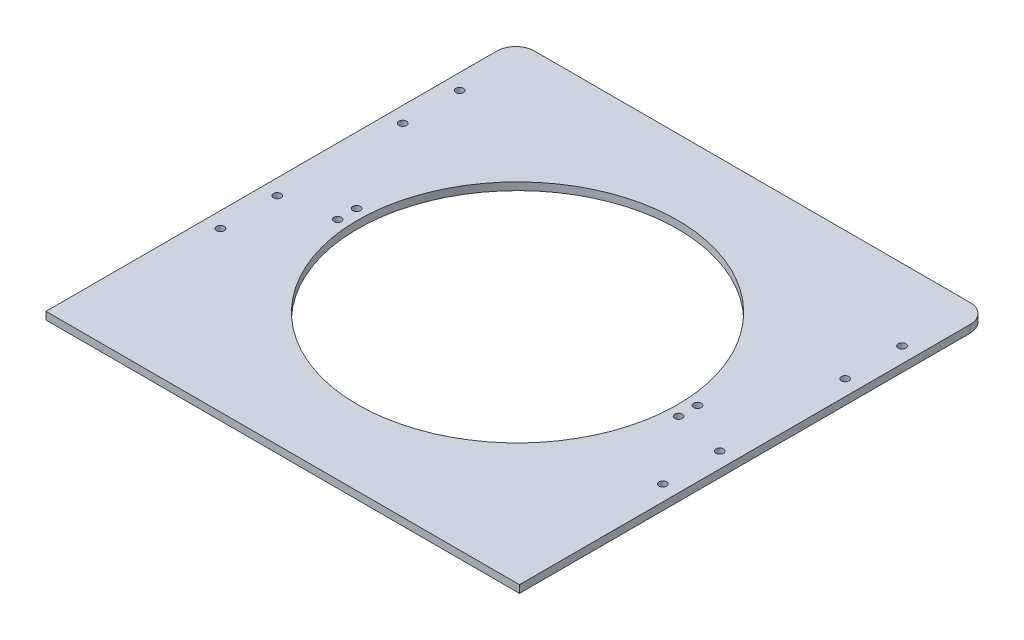
SolidWorks part; units mm, degrees
material "Medium density fiberboard, parallel to board"
ref_plane "Alzado" through (0, 0, 0) normal (0, 0, 1) x (1, 0, 0)
ref_plane "Planta" through (0, 0, 0) normal (0, 1, 0) x (1, 0, 0)
ref_plane "Vista lateral" through (0, 0, 0) normal (1, 0, 0) x (0, 0, -1)
sketch "Croquis1" plane through (0, 0, 0) normal (0, 1, 0) x (1, 0, 0)
  line L1 (-125, -124) -> (125, -124)
  line L2 (-125, -124) -> (-125, 114)
  line L3 (-115, 124) -> (115, 124)
  line L4 (125, -124) -> (125, 114)
  line L5 (-125, -124) -> (125, 124) construction
  line L6 (-125, 124) -> (125, -124) construction
  arc A0 (115, 124) -> (125, 114) centre (115, 114) cw
  arc A1 (-125, 114) -> (-115, 124) centre (-115, 114) cw
  point P0 (0, 0)
  dimension "D3" = 10
  dimension "D1" = 250
  dimension "D2" = 248
extrude "Saliente-Extruir1" add sketch "Croquis1" along normal blind 4
sketch "Croquis2" plane through (0, 4, 0) normal (0, 1, 0) x (1, 0, 0)
  line L0 (-125, 0) -> (125, 0) construction
  line L1 (-125, 114) -> (-125, -124) construction
  line L2 (125, -124) -> (125, 114) construction
  line L3 (0, 84.42) -> (0, -84.42) construction
  circle A0 centre (0, 0) radius 84.42
  circle A1 centre (-90, 5) radius 2
  circle A2 centre (-90, -5) radius 2
  circle A3 centre (90, -5) radius 2
  circle A4 centre (90, 5) radius 2
  dimension "D1" = 168.84
  dimension "D2" = 4
  dimension "D3" = 4
  dimension "D4" = 10
  dimension "D5" = 5
  dimension "D6" = 90
  dimension "D7" = 90
extrude "Cortar-Extruir1" cut sketch "Croquis2" against normal blind 4
sketch "Croquis3" plane through (0, 4, 0) normal (0, 1, 0) x (1, 0, 0)
  line L0 (115, 124) -> (-115, 124) construction
  line L1 (-125, 114) -> (-125, -124) construction
  line L2 (0, 33.527) -> (0, -33.527) construction
  circle A0 centre (-116.8, 86.2) radius 2
  circle A1 centre (-116.8, 56.15) radius 2
  circle A2 centre (-116.8, -10.05) radius 2
  circle A3 centre (-116.8, -40.1) radius 2
  circle A4 centre (116.8, -40.1) radius 2
  circle A5 centre (116.8, -10.05) radius 2
  circle A6 centre (116.8, 56.15) radius 2
  circle A7 centre (116.8, 86.2) radius 2
  point P15 (0, 0)
  dimension "D5" = 4
  dimension "D6" = 4
  dimension "D9" = 4
  dimension "D10" = 4
  dimension "D1" = 30.05
  dimension "D2" = 37.8
  dimension "D3" = 8.2
  dimension "D4" = 8.2
  dimension "D7" = 30.05
  dimension "D8" = 66.2
  dimension "D11" = 8.2
  dimension "D12" = 8.2
extrude "Cortar-Extruir2" cut sketch "Croquis3" against normal blind 10
